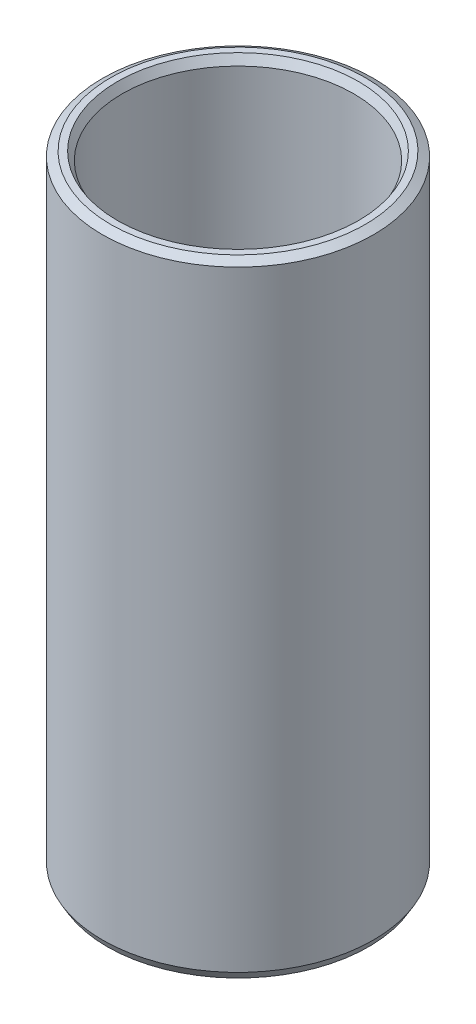
SolidWorks part; units mm, degrees
ref_plane "Front Plane" through (0, 0, 0) normal (0, 0, 1) x (1, 0, 0)
ref_plane "Top Plane" through (0, 0, 0) normal (0, 1, 0) x (1, 0, 0)
ref_plane "Right Plane" through (0, 0, 0) normal (1, 0, 0) x (0, 0, -1)
sketch "Sketch1" plane through (0, 0, 0) normal (0, 1, 0) x (1, 0, 0)
  circle A0 centre (0, 0) radius 45
  dimension "SLEEVE_OD" = 90
extrude "Boss-Extrude1" add sketch "Sketch1" along normal blind 207.1548
sketch "Sketch2" plane through (0, 0, 0) normal (0, 1, 0) x (1, 0, 0)
  circle A0 centre (0, 0) radius 38.4409
  dimension "BORE_D" = 76.8818
extrude "Cut-Extrude1" cut sketch "Sketch2" along normal through all
chamfer "Chamfer1" distance 1.5815 angle 60 4 edges at (0, 207.1548, 38.4409) (0, 0, 38.4409) (0, 0, 45) (0, 207.1548, 45) first distance on face at (0, 207.1548, 38.4409) first distance on face at (0, 0, 38.4409) first distance on face at (0, 207.1548, 45)
